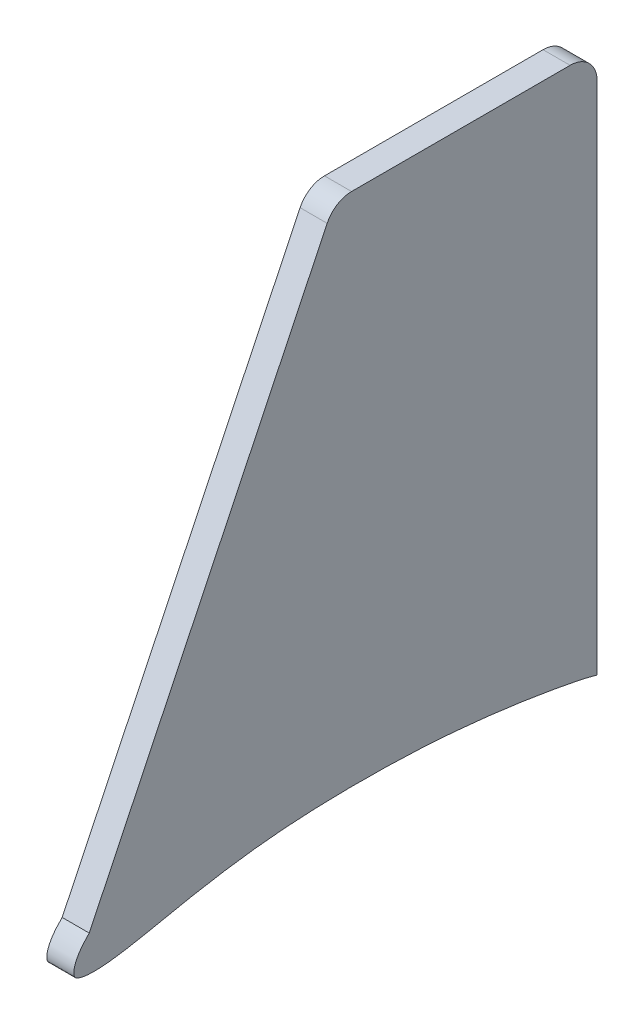
SolidWorks part; units mm, degrees
material "Balsa"
ref_plane "Front Plane" through (0, 0, 0) normal (0, 0, 1) x (1, 0, 0)
ref_plane "Top Plane" through (0, 0, 0) normal (0, 1, 0) x (1, 0, 0)
ref_plane "Right Plane" through (0, 0, 0) normal (1, 0, 0) x (0, 0, -1)
sketch "Sketch4" plane through (0, 0, 0) normal (1, 0, 0) x (0, 0, -1)
  line L0 (-193, 0) -> (-97, 200)
  line L1 (-97, 200) -> (0, 200)
  line L2 (0, 200) -> (0, 0)
  spline S0 degree 3 poles (-1.5176, 0.4745) (0.3712, -0.1398) (-1.3741, 0.6074) (-2.6309, 1.3623) (-5.4839, 2.965) (-8.7837, 4.7948) (-13.043, 6.7528) (-18.109, 8.724) (-23.9972, 10.8251) (-30.6217, 13.0458) (-37.8893, 15.3571) (-45.6905, 17.7213) (-53.9174, 20.0851) (-62.4582, 22.398) (-71.2039, 24.5977) (-80.0497, 26.6123) (-88.8919, 28.3805) (-97.6589, 29.8143) (-106.3145, 30.7914) (-114.8264, 31.2953) (-123.1638, 31.3356) (-131.2817, 30.931) (-139.1325, 30.1038) (-146.6605, 28.8851) (-153.8095, 27.3318) (-160.5154, 25.4841) (-166.7147, 23.3773) (-172.3529, 21.0541) (-177.3818, 18.5573) (-181.7627, 15.9345) (-185.4631, 13.2361) (-188.4629, 10.5193) (-190.7503, 7.8494) (-192.3194, 5.2922) (-193.1211, 3.0859) (-193.2999, 1.56) (-193.2171, 0.757) (-193.1352, 0.3646) (-193.0471, 0.1095) (-192.9664, -0.0801) (-192.8945, -0.2092) (-192.8132, -0.3294) (-192.7111, -0.436) (-192.595, -0.5361) (-192.4186, -0.673) (-192.1592, -0.8274) (-191.7435, -1.0325) (-191.231, -1.227) (-189.8781, -1.6344) (-187.3563, -1.9311) (-183.3634, -1.9068) (-178.3375, -1.4146) (-172.2514, -0.4575) (-165.0448, 0.9718) (-156.6725, 2.7481) (-147.1324, 4.6131) (-136.5389, 6.392) (-125.0887, 7.9217) (-113.0434, 8.9908) (-100.7165, 9.5573) (-88.3856, 9.7404) (-76.2557, 9.5884) (-64.5104, 9.1201) (-53.345, 8.3385) (-42.948, 7.3126) (-33.4763, 6.1536) (-25.0385, 4.9407) (-17.7566, 3.751) (-11.6114, 2.6292) (-6.909, 1.7129) (-3.101, 0.8159) (-1.5176, 0.4745) (0.3712, -0.1398) (-1.3741, 0.6074) knots -0.016237 -0.007308 -0.001841 0 0.001813 0.006911 0.014576 0.024172 0.035572 0.049013 0.064513 0.081849 0.100772 0.120997 0.142228 0.164173 0.186537 0.209023 0.231367 0.25332 0.274804 0.295858 0.316449 0.336531 0.356033 0.374893 0.39299 0.410197 0.426388 0.441459 0.455334 0.467938 0.479236 0.489204 0.497851 0.505194 0.511308 0.515097 0.516441 0.517273 0.51806 0.518436 0.518797 0.519154 0.519508 0.519887 0.520289 0.52116 0.522116 0.52372 0.525214 0.532575 0.542381 0.554776 0.569931 0.588005 0.609188 0.633329 0.660001 0.688743 0.718873 0.749543 0.780127 0.810209 0.839387 0.867183 0.893104 0.91676 0.937874 0.956199 0.971544 0.983763 0.992692 0.998159 1 1.001813 1.006911 1.014576 only from (0, 0) to (0, 0)
  dimension "D1" = 200
  dimension "D2" = 97
  dimension "D3" = 193
extrude "Boss-Extrude1" add sketch "Sketch4" along normal blind 10 contours S0 L2 L1 L0 | L2 S0 L0 | L0 S0 region at (0, 5.432, 191.1011) region at (0, 15.544, 115.6964) region at (0, 101.7524, 69.8061)
fillet "Fillet1" radius 10 1 edges at (5, 200, 97)
fillet "Fillet2" radius 10 1 edges at (5, 200, 0)
ref_plane "Plane1" through (0, 1.45, 0) normal (0, 1, 0) x (1, 0, 0)
